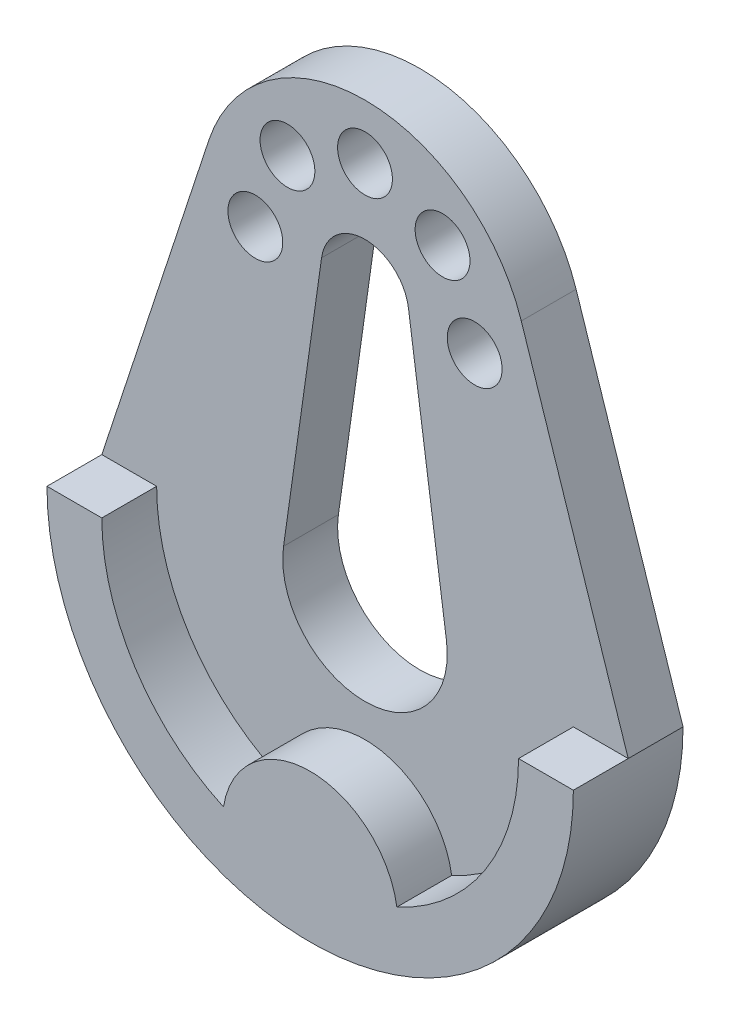
SolidWorks part; units mm, degrees
material "AISI 304"
ref_plane "Front Plane" through (0, 0, 0) normal (0, 0, 1) x (1, 0, 0)
ref_plane "Top Plane" through (0, 0, 0) normal (0, 1, 0) x (1, 0, 0)
ref_plane "Right Plane" through (0, 0, 0) normal (1, 0, 0) x (0, 0, -1)
sketch "Sketch1" plane through (0, 0, 0) normal (0, 0, 1) x (1, 0, 0)
  line L0 (14.8523, 2.1) -> (7.9212, 51.12)
  line L1 (-7.9212, 51.12) -> (-14.8523, 2.1)
  line L2 (48, 0) -> (28.5019, 59.3618)
  line L3 (-28.5019, 59.3618) -> (-48, 0)
  line L4 (-48, 0) -> (-38, 0)
  line L5 (38, 0) -> (48, 0)
  arc A0 (-14.8523, 2.1) -> (14.8523, 2.1) centre (0, 0) ccw
  arc A1 (7.9212, 51.12) -> (-7.9212, 51.12) centre (0, 50) ccw
  arc A2 (28.5019, 59.3618) -> (-28.5019, 59.3618) centre (0, 50) ccw
  arc A3 (-48, 0) -> (48, 0) centre (0, 0) ccw
  arc A4 (-38, 0) -> (-15.8119, -34.5541) centre (0, 0) ccw
  arc A5 (-15.8119, -34.5541) -> (15.8119, -34.5541) centre (0, -37) cw
  arc A6 (15.8119, -34.5541) -> (38, 0) centre (0, 0) ccw
  circle A8 centre (-20, 50) radius 5
  circle A9 centre (-14.1421, 64.1421) radius 5
  circle A10 centre (0, 70) radius 5
  circle A11 centre (14.1421, 64.1421) radius 5
  circle A12 centre (20, 50) radius 5
  circle A13 centre (0, 50) radius 20 construction
  point P23 (0, -48)
  point P25 (0, 0)
  point P27 (0, 0)
  point P36 (0, 0)
  point P37 (0, 0)
  dimension "D1" = 48
  dimension "D2" = 15
  dimension "D3" = 8
  dimension "D5" = 16
  dimension "D7" = 38
  dimension "D9" = 30
  dimension "D11" = 10
  dimension "D4" = 50
  dimension "D6" = 37
  dimension "D8" = 10
  dimension "D10" = 20
  dimension "D12" = 5
extrude "Boss-Extrude1" add sketch "Sketch1" along normal blind 10 contours A5 A6 L5 L2 A2 L3 L4 A4 A12 A11 A10 A9 A8 A1 L0 A0 L1 region at (43, 1.4946, 0)
extrude "Boss-Extrude2" add sketch "Sketch1<3>" along normal blind 20 contours A6 A5 A4 L4 A3 L5 region at (0, -28.1064, 0)
sketch "Sketch1<3>" plane through (0, 0, 0) normal (0, 0, 1) x (1, 0, 0) same geometry as "Sketch1"
